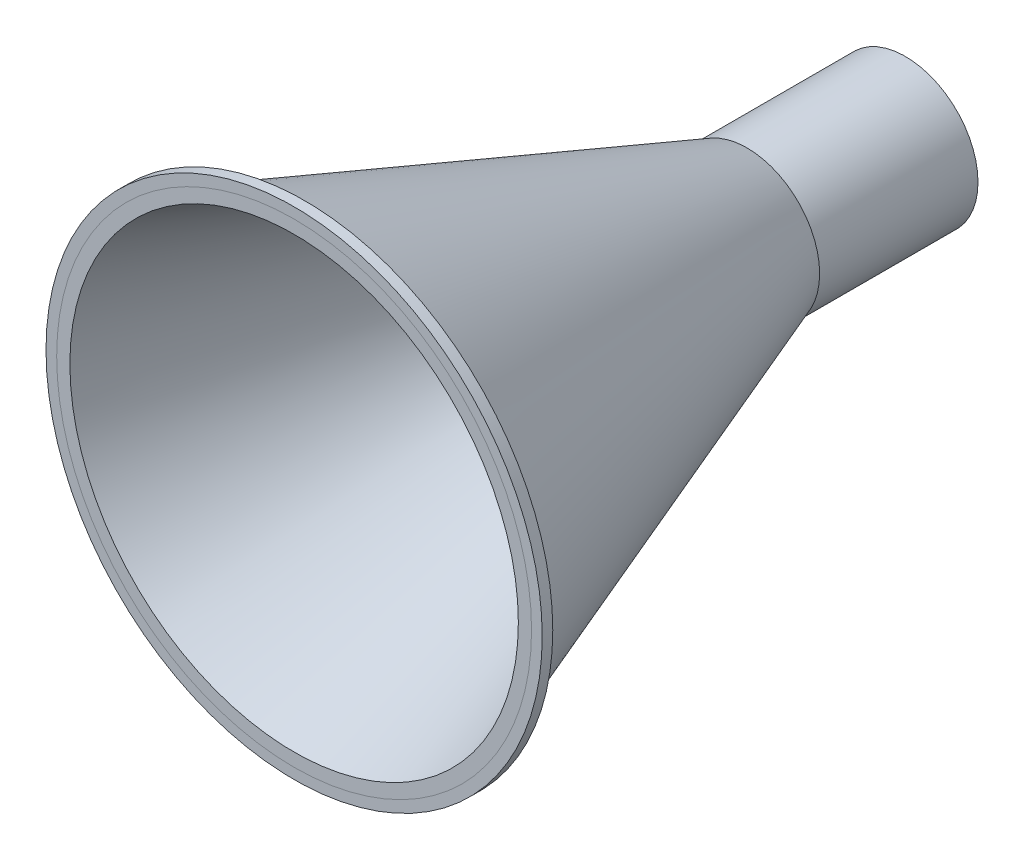
SolidWorks part; units mm, degrees
ref_plane "Front Plane" through (0, 0, 0) normal (0, 0, 1) x (1, 0, 0)
ref_plane "Top Plane" through (0, 0, 0) normal (0, 1, 0) x (1, 0, 0)
ref_plane "Right Plane" through (0, 0, 0) normal (1, 0, 0) x (0, 0, -1)
sketch "Sketch13" plane through (0, 0, 0) normal (0, 0, 1) x (1, 0, 0)
  circle A0 centre (0, 0) radius 17.4625
  dimension "D1" = 34.925
extrude "Boss-Extrude5" add sketch "Sketch13" along normal blind 108.966 draft 20 draft outward yes
sketch "Sketch14" plane through (0, 0, 0) normal (0, 0, -1) x (-1, 0, 0)
  circle A0 centre (0, 0) radius 14.2875
  dimension "D1" = 28.575
extrude "Cut-Extrude3" cut sketch "Sketch14" against normal blind 108.966 draft 20 draft outward yes
sketch "Sketch17" plane through (0, 0, 0) normal (0, 0, -1) x (-1, 0, 0)
  circle A0 centre (0, 0) radius 17.4625
  circle A1 centre (0, 0) radius 12.7
extrude "Boss-Extrude6" add sketch "Sketch17" along normal blind 38.1
chamfer "Chamfer2" distance 2.54 angle 45 1 edges at (-12.7, 0, -38.1)
thread "Thread1" pitch 2.1167 method cut profile "Thread Profile2" start angle 0, offset 0, length 25.4, pitch 2.1167, diameter 25.4
ref_plane "Plane6" through (12.7, 0, -35.56) normal (0, -1, 0) x (1, 0, 0)
sketch "Thread Profile2" plane through (12.7, 0, -35.56) normal (0, -1, 0) x (1, 0, 0)
  line L0 (0, 0) -> (0, 2.1167) construction
  line L1 (0, 0) -> (1.1457, 0.6615)
  line L2 (1.1457, 0.6615) -> (1.1457, 0.926)
  line L3 (1.1457, 0.926) -> (0, 1.5875)
  line L4 (1.1457, 0.7937) -> (0, 0.7937) construction
  line L11 (0, 0) -> (0, 1.5875)
  point P2 (0, 0)
  dimension "Pitch" = 2.1167
  dimension "Profile_Angle" = 60
  dimension "Profile_Land" = 0.2646
  dimension "Profile_Height" = 1.1457
sketch "Sketch26" plane through (0, 0, 108.966) normal (0, 0, 1) x (1, 0, 0)
  circle A0 centre (0, 0) radius 59.69
  circle A1 centre (0, 0) radius 57.1229
  dimension "D1" = 119.38
extrude "Boss-Extrude7" add sketch "Sketch26" against normal blind 2.54 separate body
